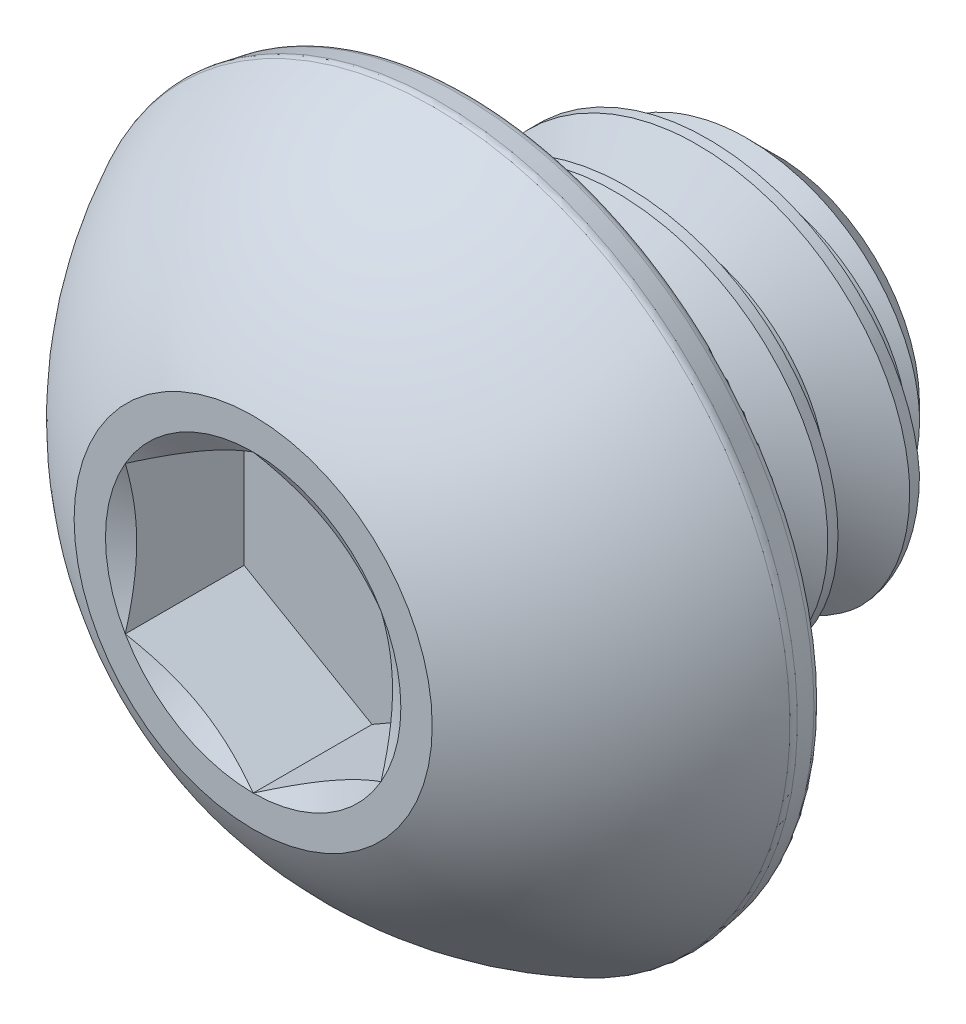
SolidWorks part; units mm, degrees
ref_plane "Front Plane" through (0, 0, 0) normal (0, 0, 1) x (1, 0, 0)
ref_plane "Top Plane" through (0, 0, 0) normal (0, 1, 0) x (1, 0, 0)
ref_plane "Right Plane" through (0, 0, 0) normal (1, 0, 0) x (0, 0, -1)
sketch "Sketch1" plane through (0, 0, 0) normal (1, 0, 0) x (0, 0, -1)
  line L0 (-4.0577, 0) -> (4.0577, 0) construction
  line L1 (-4.0577, 0) -> (-4.0577, 5.5499)
  line L2 (-4.0577, 5.5499) -> (-0.7048, 5.5499)
  line L3 (-0.7048, 5.5499) -> (-0.7048, 3.175)
  line L4 (-0.7048, 3.175) -> (4.0577, 3.175)
  line L5 (4.0577, 3.175) -> (4.0577, 0)
  point P2 (0, 0)
  point P4 (2.7876, 0)
  point P9 (2.1526, 3.175)
  point P10 (2.1526, -3.175)
  point P11 (4.0576, -3.175)
  point P15 (-2.2136, 0)
  dimension "Head Height" = 3.3528
  dimension "Head Diameter" = 11.0998
  dimension "Length" = 4.7625
  dimension "Screw Size Decimal Equivalent" = 6.35
  dimension "Thread Pitch" = 1.27
  dimension "D1" = 1.905
  dimension "D2" = 1.844
sketch "Sketch2" plane through (0, 0, 0) normal (0, 0, 1) x (1, 0, 0)
  line L0 (0, 3.175) -> (0, 0) construction
  line L1 (0, 2.2914) -> (-1.9844, 1.1457)
  line L2 (-1.9844, 1.1457) -> (-1.9844, -1.1457)
  line L3 (-1.9844, -1.1457) -> (0, -2.2914)
  line L4 (0, -2.2914) -> (1.9844, -1.1457)
  line L5 (1.9844, -1.1457) -> (1.9844, 1.1457)
  line L6 (1.9844, 1.1457) -> (0, 2.2914)
  circle A0 centre (0, 0) radius 1.9844 construction
  circle A1 centre (0, 0) radius 2.7781
  point P10 (0, 2.7781)
  dimension "D1" = 5.5563
  dimension "Drive Size" = 3.9688
sketch "Sketch3" plane through (0, 0, 0) normal (1, 0, 0) x (0, 0, -1)
  line L0 (-4.0577, 0) -> (-4.0577, 2.7781)
  line L1 (-4.0577, 0) -> (-4.0577, 5.5499) construction
  line L2 (-4.0577, 5.5499) -> (-0.7048, 5.5499) construction
  line L3 (-1.2078, 5.5499) -> (-0.7048, 5.4612)
  line L4 (-0.7048, 5.5499) -> (-0.7048, 3.175) construction
  line L5 (-0.7048, 5.4612) -> (-0.7048, 3.175)
  line L6 (-4.0577, 0) -> (4.0577, 0) construction
  line L7 (-4.0577, 0) -> (4.0577, 0)
  line L8 (4.0577, 0) -> (4.0577, 2.2225)
  line L9 (4.0577, 3.175) -> (4.0577, 0) construction
  line L10 (4.0577, 2.2225) -> (3.1051, 3.175)
  line L11 (-0.7048, 3.175) -> (4.0577, 3.175) construction
  line L12 (3.1051, 3.175) -> (-0.7048, 3.175)
  arc A0 (-4.0577, 2.7781) -> (-1.2078, 5.5499) centre (1.4172, 0) cw
  dimension "D1" = 0.5029
  dimension "D2" = 10
  dimension "D3" = 45
  dimension "D4" = 0.9525
revolve "Revolve1" add sketch "Sketch3" angle 360 about L7
sketch "Sketch4" plane through (0, 0, 4.0577) normal (0, 0, 1) x (1, 0, 0)
  line L0 (-1.9844, -1.1457) -> (0, -2.2914) construction
  line L1 (-1.9844, 1.1457) -> (-1.9844, -1.1457) construction
  line L2 (0, 2.2914) -> (-1.9844, 1.1457) construction
  line L3 (1.9844, 1.1457) -> (0, 2.2914) construction
  line L4 (1.9844, -1.1457) -> (1.9844, 1.1457) construction
  line L5 (0, -2.2914) -> (1.9844, -1.1457) construction
  line L6 (-1.9844, -1.1457) -> (0, -2.2914)
  line L7 (-1.9844, 1.1457) -> (-1.9844, -1.1457)
  line L8 (0, 2.2914) -> (-1.9844, 1.1457)
  line L9 (1.9844, 1.1457) -> (0, 2.2914)
  line L10 (1.9844, -1.1457) -> (1.9844, 1.1457)
  line L11 (0, -2.2914) -> (1.9844, -1.1457)
extrude "Cut-Extrude1" cut sketch "Sketch4" against normal up to vertex (1.844 mm away) up to point (0, 0, 2.2136)
sketch "Sketch5" plane through (0, 0, 4.0577) normal (0, 0, 1) x (1, 0, 0)
  circle A0 centre (0, 0) radius 2.2914
extrude "Cut-Extrude2" cut sketch "Sketch5" against normal up to vertex (1.844 mm away) draft 60 up to point (0, 0, 2.2136)
fillet "Fillet1" radius 0.1676 2 edges at (5.5499, 0, 1.2078) (5.4612, 0, 0.7048)
split "Split1" bodies to split 106 resulting bodies 107 108 split by face at (5.3206, 0, 0.7048)
sketch "Sketch6" plane through (0, 0, -4.0577) normal (0, 0, -1) x (-1, 0, 0)
  circle A0 centre (0, 0) radius 3.175 construction
  circle A1 centre (0, 0) radius 3.175
curve "Helix/Spiral1" pitch 1.27 height 6.0325 radius 3.175 centre (0, 0, -4.0577) axis (0, 0, 1) start towards (0, 1, 0)
sketch "Sketch7" plane through (0, 0, 0) normal (1, 0, 0) x (0, 0, -1)
  line L0 (3.9783, 3.3125) -> (4.6133, 2.2126) construction
  line L1 (4.6133, 2.2126) -> (5.2483, 3.3125) construction
  line L2 (5.2483, 3.3125) -> (3.9783, 3.3125) construction
  line L3 (4.018, 3.2437) -> (5.2086, 3.2437)
  line L4 (5.2086, 3.2437) -> (4.6927, 2.3501)
  line L5 (4.6927, 2.3501) -> (4.5339, 2.3501)
  line L6 (4.5339, 2.3501) -> (4.018, 3.2437)
  line L7 (4.6133, 2.3501) -> (4.6133, 2.2126) construction
  line L8 (4.0577, 3.175) -> (5.1689, 3.175) construction
  line L9 (4.6133, 3.3125) -> (4.6133, 3.175) construction
  point P12 (4.6133, 3.2437)
  dimension "D1" = 1.27
  dimension "D2" = 0.1588
sweep "Cut-Sweep1" cut profiles "Sketch7" path "Helix/Spiral1" align with end faces yes
sketch "Sketch8" plane through (0, 0, 0.7048) normal (0, 0, -1) x (-1, 0, 0)
  circle A0 centre (0, 0) radius 3.3125
extrude "Boss-Extrude1" add sketch "Sketch8" along normal up to vertex (2.8575 mm away) draft 45 up to point (0, 3.175, -2.1526)
equation "\"D1@Sketch1\"=\"Thread Pitch@Sketch1\"*1.5"
equation "\"D2@Sketch1\"=0.55*\"Head Height@Sketch1\""
equation "\"D1@Sketch2\"=\"Drive Size@Sketch2\"*1.4"
equation "\"D1@Sketch3\"=0.15*\"Head Height@Sketch1\""
equation "\"D4@Sketch3\"=0.75*\"Thread Pitch@Sketch1\""
equation "\"D1@Fillet1\"=.05*\"Head Height@Sketch1\""
equation "\"D4@Helix/Spiral1\"=\"Thread Pitch@Sketch1\""
equation "\"D3@Helix/Spiral1\"=\"Length@Sketch1\"+\"Thread Pitch@Sketch1\""
equation "\"D2@Sketch7\"=\"D1@Sketch7\"/8"
equation "\"D1@Sketch7\"=\"Thread Pitch@Sketch1\""
